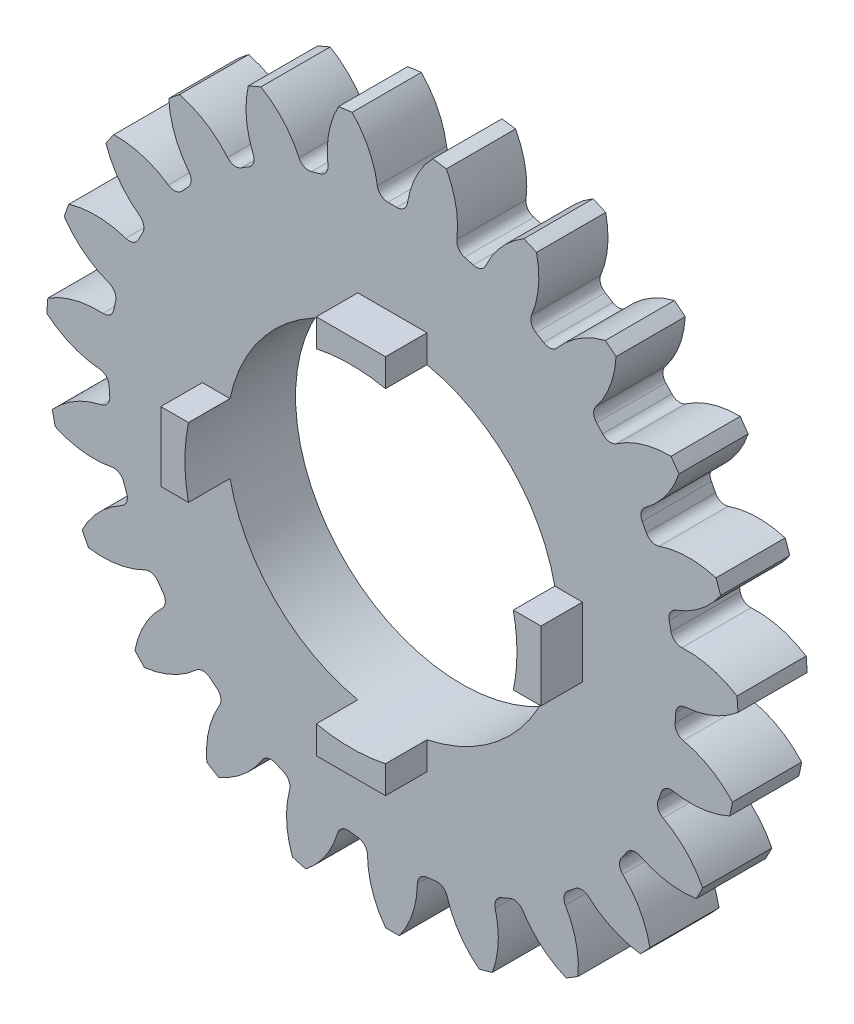
SolidWorks part; units mm, degrees
ref_plane "Front Plane" through (0, 0, 0) normal (0, 0, 1) x (1, 0, 0)
ref_plane "Top Plane" through (0, 0, 0) normal (0, 1, 0) x (1, 0, 0)
ref_plane "Right Plane" through (0, 0, 0) normal (1, 0, 0) x (0, 0, -1)
sketch "Sketch1" plane through (0, 0, 0) normal (0, 0, 1) x (1, 0, 0)
  line L4 (-1.0191, 20.4747) -> (0, 0) construction
  line L5 (0, 0) -> (0, 25) construction
  line L6 (0, 0) -> (3.4042, 24.7671) construction
  line L7 (-1.6208, 22.9428) -> (0.7618, 24.0057) construction
  line L8 (-1.6208, 22.9428) -> (0.3993, 23.0855) construction
  line L11 (1.6208, 22.9428) -> (-1.6208, 22.9428) construction
  circle A0 centre (0, 0) radius 20.5
  circle A1 centre (0, 0) radius 23 construction
  circle A2 centre (0, 0) radius 25
  arc A3 (-2.9082, 24.8303) -> (-1.0191, 20.4747) centre (-7.7586, 20.1392) cw
  arc A4 (2.9082, 24.8303) -> (1.0191, 20.4747) centre (7.7586, 20.1392) ccw
  point P5 (-23, 0)
  point P6 (-25, 0)
  point P7 (-20.5, 0)
  point P12 (-1.6208, 22.9428)
  point P22 (1.6208, 22.9428)
  dimension "D5" = 46
  dimension "D1" = 2.5
  dimension "D2" = 2
  dimension "D3" = 20
  dimension "D4" = 3.2416
  dimension "D6" = 7.826
  dimension "D7" = 0.5
extrude "Boss-Extrude1" add sketch "Sketch1" against normal blind 5 contours A2
extrude "Cut-Extrude1" cut sketch "Sketch1<4>" against normal blind 10 contours A4 A2 A3 A0 region at (0, 23.1422, 0)
sketch "Sketch1<4>" plane through (0, 0, 0) normal (0, 0, 1) x (1, 0, 0) same geometry as "Sketch1"
fillet "Fillet2" radius 0.76 2 edges at (1.0191, 20.4747, -2.5) (-1.0191, 20.4747, -2.5)
ref_axis "Axis1" through (0, 0, 0) along (0, 0, 1)
pattern_circular "CirPattern2" count 23 over 360 about axis through (0, 0, 0) along (0, 0, 1) of "Cut-Extrude1", "Fillet2"
sketch "Sketch2" plane through (0, 0, 0) normal (0, 0, 1) x (1, 0, 0)
  circle A0 centre (0, 0) radius 12
  dimension "D1" = 24
extrude "Cut-Extrude2" cut sketch "Sketch2" against normal up to surface (5 mm away) up to face at (0, 0, -5)
sketch "Sketch3" plane through (0, 0, 0) normal (0, 0, 1) x (1, 0, 0)
  line L0 (-2.5, 11.7367) -> (-2.5, 13.7367)
  line L1 (-2.5, 13.7367) -> (2.5, 13.7367)
  line L2 (2.5, 13.7367) -> (2.5, 11.7367)
  line L3 (0, 0) -> (0, 12) construction
  line L4 (13.7367, -2.5) -> (11.7367, -2.5)
  line L5 (13.7367, 2.5) -> (13.7367, -2.5)
  line L6 (11.7367, 2.5) -> (13.7367, 2.5)
  line L7 (-2.5, -13.7367) -> (-2.5, -11.7367)
  line L8 (2.5, -13.7367) -> (-2.5, -13.7367)
  line L9 (2.5, -11.7367) -> (2.5, -13.7367)
  line L10 (-13.7367, 2.5) -> (-11.7367, 2.5)
  line L11 (-13.7367, -2.5) -> (-13.7367, 2.5)
  line L12 (-11.7367, -2.5) -> (-13.7367, -2.5)
  circle A0 centre (0, 0) radius 12 construction
  arc A1 (-2.5, 11.7367) -> (2.5, 11.7367) centre (0, 0) cw
  arc A2 (11.7367, 2.5) -> (11.7367, -2.5) centre (0, 0) cw
  arc A3 (2.5, -11.7367) -> (-2.5, -11.7367) centre (0, 0) cw
  arc A4 (-11.7367, -2.5) -> (-11.7367, 2.5) centre (0, 0) cw
  point P24 (0, 0)
  dimension "D4" = 4
  dimension "D1" = 2.5
  dimension "D2" = 2.5
  dimension "D3" = 2
extrude "Boss-Extrude2" add sketch "Sketch3" along normal blind 3
equation "\"backlash\"= 0.1mm"
equation "\"module\"= 2mm"
equation "\"pressureAngle\"= 20deg"
equation "\"width\"= 10mm"
equation "\"D1@Sketch1\"= 1.25 * \"module\""
equation "\"D2@Sketch1\"=\"module\""
equation "\"D5@Sketch1\"=\"module\"*\"numberOfTeeth\""
equation "\"D1@Boss-Extrude1\"=\"width\"-5"
equation "\"D3@Sketch1\"=\"pressureAngle\""
equation "\"D1@Cut-Extrude1\"=\"width\""
equation "\"D1@CirPattern2\"=\"numberOfTeeth\""
equation "\"D1@Fillet2\"=0.38*\"module\""
equation "\"D4@Sketch1\"=pi*\"module\"/2+\"backlash\""
equation "\"numberOfTeeth\"= 23"
equation "\"D6@Sketch1\"=180/\"numberOfTeeth\""
equation "\"toothTipProfile\"= 1mm"
equation "\"D7@Sketch1\"=\"toothTipProfile\"/2"
equation "\"lengthOverallRack\"= pi * \"module\" * \"numberOfTeethRack\""
equation "\"numberOfTeethRack\"= 20"
